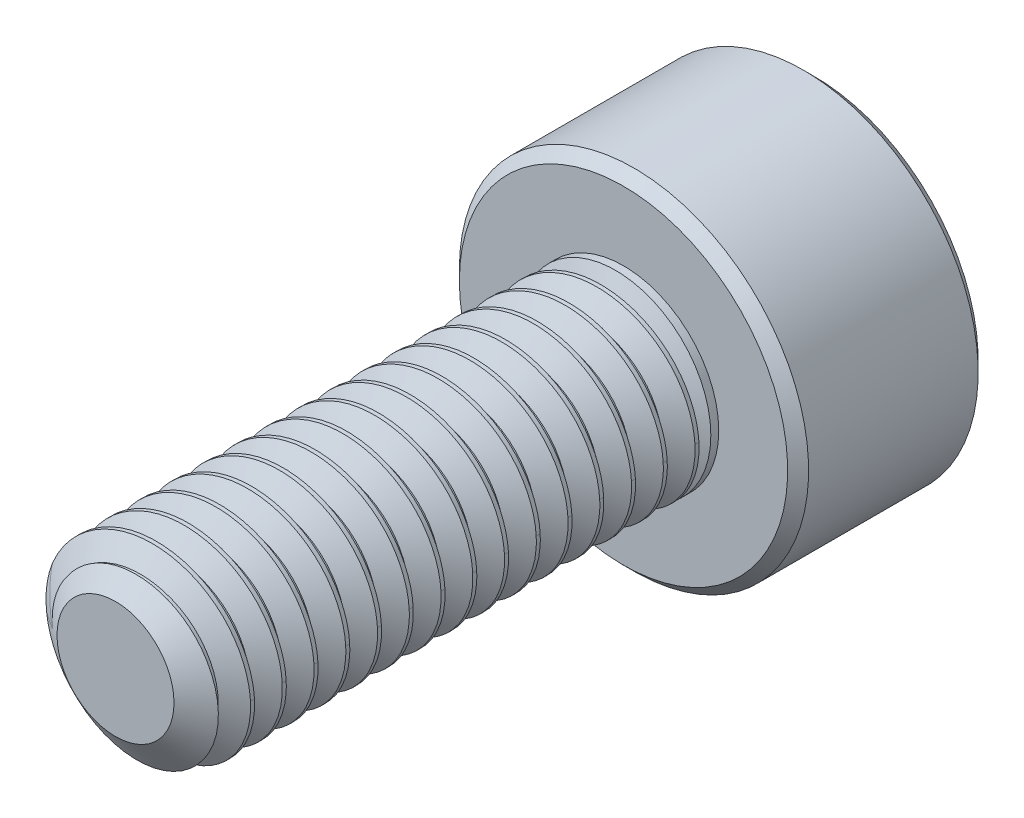
SolidWorks part; units mm, degrees
ref_plane "Front Plane" through (0, 0, 0) normal (0, 0, 1) x (1, 0, 0)
ref_plane "Top Plane" through (0, 0, 0) normal (0, 1, 0) x (1, 0, 0)
ref_plane "Right Plane" through (0, 0, 0) normal (1, 0, 0) x (0, 0, -1)
sketch "Sketch1" plane through (0, 0, 0) normal (0, 0, 1) x (1, 0, 0)
  circle A0 centre (0, 0) radius 1.5
  dimension "OD" = 3
extrude "Extrude1" add sketch "Sketch1" against normal blind 8
sketch "Sketch2" plane through (0, 0, 0) normal (0, 0, 1) x (1, 0, 0)
  circle A0 centre (0, 0) radius 1.5 construction
  circle A1 centre (0, 0) radius 1.5
curve "Helix/Spiral1" pitch 0.5 height 8.5 radius 1.5 centre (0, 0, 0) axis (0, 0, -1) start towards (0, 1, 0) parameters "pitch"=0.5
sketch "Sketch3" plane through (0, 0, 0) normal (1, 0, 0) x (0, 0, -1)
  line L0 (-0.4375, 1.5) -> (-0.25, 1.1752)
  line L1 (-0.25, 1.1752) -> (-0.1875, 1.1752)
  line L2 (-0.1875, 1.1752) -> (0, 1.5)
  line L3 (-0.4375, 1.5) -> (0, 1.5)
  line L4 (-0.2188, 1.5) -> (-0.2188, 1.1752) construction
  line L5 (-0.3438, 1.3376) -> (-0.0938, 1.3376) construction
  line L6 (0, 1.5) -> (0, -1.5) construction
  line L7 (0, -1.5) -> (8, -1.5) construction
  point P11 (2.25, -1.5)
  dimension "D1" = 0.0625
  dimension "D2" = 0.25
  dimension "D3" = 60
  dimension "D4" = 2.25
sweep "Cut-Sweep1" cut profiles "Sketch3" path "Helix/Spiral1" align with end faces yes
sketch "Sketch4" plane through (0, 0, 0) normal (1, 0, 0) x (0, 0, -1)
  line L0 (0.4053, 1.5) -> (0, 0.9212)
  line L1 (0, 0.9212) -> (0, 1.5)
  line L2 (0.4053, 1.5) -> (0, 1.5)
  line L3 (-0.4375, 1.5) -> (0, 1.5) construction
  line L4 (0, 0) -> (7.0209, 0) construction
  dimension "D1" = 55
  dimension "D2" = 0.254
revolve "Cut-Revolve1" cut sketch "Sketch4" angle 360 about L4
sketch "Sketch5" plane through (0, 0, 0) normal (1, 0, 0) x (0, 0, -1)
  line L0 (8, -1.1822) -> (8, 1.0703) construction
  line L1 (8, 1.5) -> (0.1202, 1.5)
  line L2 (8, 1.5) -> (8, 0)
  line L3 (8, 0) -> (0, 0)
  line L4 (0, 1.1698) -> (0, 0)
  line L5 (0.1202, 1.5) -> (0, 1.1698)
  line L6 (0, 0) -> (9.9695, 0) construction
  point P3 (0, 1.5)
  point P10 (0, 1.5)
  dimension "D1" = 0.3302
  dimension "D3" = 20
  dimension "Thread Min" = 0
revolve "partially thread" [suppressed] add sketch "Sketch5" angle 360 about L6
sketch "Sketch6" plane through (0, 0, -8) normal (0, 0, -1) x (-1, 0, 0)
  circle A0 centre (0, 0) radius 2.75
  dimension "head dia" = 5.5
extrude "Extrude2" add sketch "Sketch6" along normal blind 3
sketch "Sketch7" plane through (0, 0, -11) normal (0, 0, -1) x (-1, 0, 0)
  line L1 (0, 1.4434) -> (-1.25, 0.7217)
  line L2 (-1.25, 0.7217) -> (-1.25, -0.7217)
  line L3 (-1.25, -0.7217) -> (0, -1.4434)
  line L4 (0, -1.4434) -> (1.25, -0.7217)
  line L5 (1.25, -0.7217) -> (1.25, 0.7217)
  line L6 (1.25, 0.7217) -> (0, 1.4434)
  circle A0 centre (0, 0) radius 1.25 construction
  dimension "hex dia" = 2.5
extrude "Cut-Extrude1" cut sketch "Sketch7" against normal blind 1.875
sketch "Sketch8" plane through (0, 0, -11) normal (0, 0, -1) x (-1, 0, 0)
  circle A0 centre (0, 0) radius 1.4434
extrude "Cut-Extrude2" cut sketch "Sketch8" against normal through all draft 45
chamfer "Chamfer1" distance 0.165 angle 45 2 edges at (-2.75, 0, -11) (-2.75, 0, -8)
sketch "Sketch9" plane through (0, 0, 0) normal (1, 0, 0) x (0, 0, -1)
  line L0 (0, 1.5) -> (0, -1.5) construction
  line L1 (2.75, 1.5) -> (2.75, -1.5) construction
  dimension "D1" = 2.75
sketch "Sketch10" plane through (0, 0, 0) normal (1, 0, 0) x (0, 0, -1)
  line L0 (8, 1.5) -> (8, 0)
  line L1 (8, 1.5) -> (7.875, 1.5)
  line L2 (7.875, 1.5) -> (7.2537, 0)
  line L3 (8, 0) -> (7.2537, 0)
  line L4 (8, 2.585) -> (8, -2.585) construction
  dimension "D1" = 22.5
  dimension "D2" = 0.125
revolve "Revolve1" add sketch "Sketch10" angle 360 about L3
equation "\"D3@Helix/Spiral1\" = \"screw length@Extrude1\"+\"pitch@Helix/Spiral1\""
equation "\"D1@Sketch3\" = \"pitch@Helix/Spiral1\"*.125"
equation "\"D2@Sketch3\" = \"pitch@Helix/Spiral1\"*.5"
equation "\"D1@Cut-Extrude1\" = \"hex dia@Sketch7\"*.75"
equation "\"D1@Chamfer1\" = \"head dia@Sketch6\"*.03"
equation "\"D1@Sketch9\" = \"pitch@Helix/Spiral1\"*5.5"
equation "\"D2@Sketch10\" = \"pitch@Helix/Spiral1\"*.25"
equation "\"D4@Sketch3\" = \"pitch@Helix/Spiral1\"*4.50"
